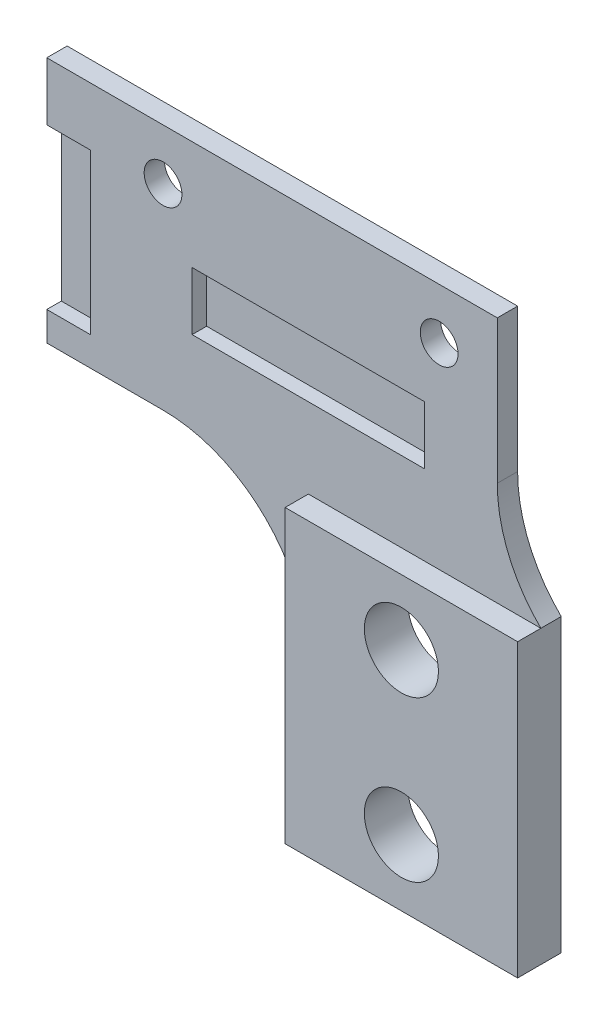
SolidWorks part; units mm, degrees
ref_plane "Front Plane" through (0, 0, 0) normal (0, 0, 1) x (1, 0, 0)
ref_plane "Top Plane" through (0, 0, 0) normal (0, 1, 0) x (1, 0, 0)
ref_plane "Right Plane" through (0, 0, 0) normal (1, 0, 0) x (0, 0, -1)
sketch "Sketch1" plane through (0, 0, 0) normal (0, 0, 1) x (1, 0, 0)
  line L1 (-20, -8.5) -> (20, -8.5)
  line L2 (-20, -8.5) -> (-20, 8.5)
  line L3 (-20, 8.5) -> (20, 8.5)
  line L4 (20, -8.5) -> (20, 8.5)
  line L5 (-20, -8.5) -> (20, 8.5) construction
  line L6 (-20, 8.5) -> (20, -8.5) construction
  point P0 (0, 0)
extrude "Boss-Extrude1" add sketch "Sketch1" along normal blind 1.4
sketch "Sketch3" plane through (0, 0, 0) normal (0, 0, 1) x (1, 0, 0)
  line L1 (20, -8.5) -> (20, 8.5) construction
  line L2 (20, 8.5) -> (20, 0.5) construction
  line L3 (20, 8.5) -> (-20, 8.5) construction
  line L4 (-20, 8.5) -> (-20, 4.5) construction
  line L5 (-1, 1) -> (15, 1)
  line L6 (-1, 1) -> (-1, -3)
  line L7 (-1, -3) -> (15, -3)
  line L8 (15, 1) -> (15, -3)
  line L10 (-20, 8.5) -> (-20, -8.5) construction
  line L11 (-20, 4.5) -> (-11, 4.5) construction
  line L13 (-11, 4.5) -> (-8, 4.5)
  line L14 (-11, 4.5) -> (-11, -6.5)
  line L15 (-11, -6.5) -> (-8, -6.5)
  line L16 (-8, 4.5) -> (-8, -6.5)
extrude "Cut-Extrude1" cut sketch "Sketch3" against normal blind 1 from surface starting at face at (0, 0, 1.4)
sketch "Sketch4" plane through (0, 0, 0) normal (0, 0, 1) x (1, 0, 0)
  line L0 (20, 8.5) -> (16, 8.5) construction
  line L1 (20, 8.5) -> (-20, 8.5) construction
  line L2 (16, 8.5) -> (16, 5) construction
  line L3 (16, 5) -> (-3, 5) construction
  circle A0 centre (16, 5) radius 1.3
  circle A1 centre (-3, 5) radius 1.3
extrude "Cut-Extrude2" cut sketch "Sketch4" along normal blind 11
sketch "Sketch7" plane through (0, 0, 0) normal (0, 0, 1) x (1, 0, 0)
  line L0 (-20, -8.5) -> (20, -8.5) construction
  line L1 (-20, 8.5) -> (-11, 8.5)
  line L2 (-20, 8.5) -> (-20, -8.5)
  line L3 (-20, -8.5) -> (-11, -8.5)
  line L4 (-11, 8.5) -> (-11, -8.5)
extrude "Cut-Extrude5" cut sketch "Sketch7" along normal blind 21
sketch "Sketch9" plane through (0, 0, 0) normal (0, 0, 1) x (1, 0, 0)
  line L0 (-3, 5) -> (16, 5) construction
  line L1 (20, -8.5) -> (15, -8.5) construction
  line L3 (15, -8.5) -> (15, -13) construction
  line L8 (-11, -8.5) -> (20, -8.5) construction
  line L9 (17.3, 5) -> (17.3, -9.7257) construction
  line L11 (23, -8.5) -> (23, -28.5414)
  line L12 (23, -28.5414) -> (7, -28.5414)
  line L13 (7, -8.5) -> (7, -28.5414)
  line L14 (15, -28.5414) -> (15, -24) construction
  line L15 (15, -24) -> (15, -13) construction
  line L16 (23, -8.5) -> (7, -8.5)
  circle A0 centre (15, -13) radius 2.55
  circle A1 centre (15, -24) radius 2.55
  circle A2 centre (16, 5) radius 1.3 construction
extrude "Boss-Extrude3" add sketch "Sketch9" along normal blind 3
fillet "Fillet1" radius 10 2 edges at (7, -8.5, 0.7) (20, -8.5, 0.7)
